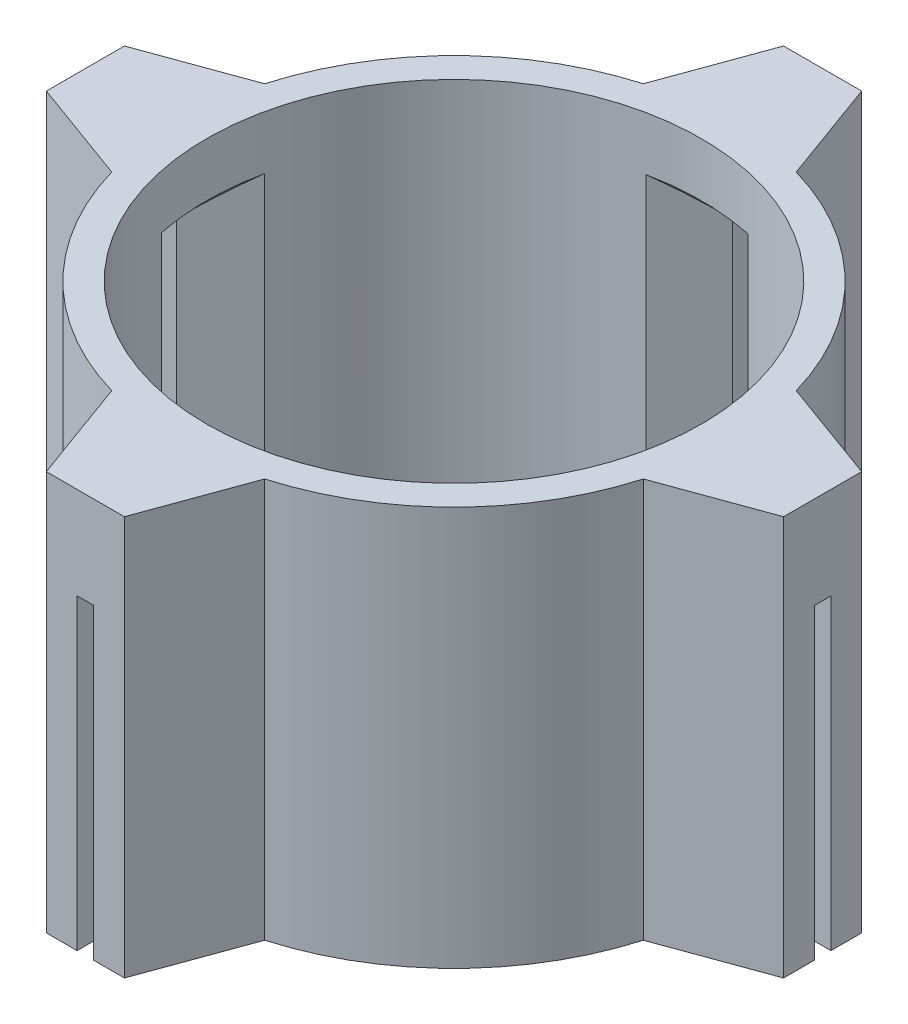
SolidWorks part; units mm, degrees
ref_plane "Front Plane" through (0, 0, 0) normal (0, 0, 1) x (1, 0, 0)
ref_plane "Top Plane" through (0, 0, 0) normal (0, 1, 0) x (1, 0, 0)
ref_plane "Right Plane" through (0, 0, 0) normal (1, 0, 0) x (0, 0, -1)
sketch "Sketch1" plane through (0, 0, 0) normal (0, 1, 0) x (1, 0, 0)
  line L0 (-60.2909, 0) -> (0, 0) construction
  line L1 (0, 49.1127) -> (0, -58.1826) construction
  line L2 (-57.1243, 1.7145) -> (-51.0887, 1.7145)
  line L3 (-57.1243, -1.7145) -> (-51.0887, -1.7145)
  line L4 (51.0887, 1.7145) -> (57.1243, 1.7145)
  line L5 (51.0887, -1.7145) -> (57.1243, -1.7145)
  line L6 (-1.7145, -51.0887) -> (-1.7145, -57.1243)
  line L7 (1.7145, -51.0887) -> (1.7145, -57.1243)
  line L8 (-1.7145, 57.1243) -> (-1.7145, 51.0887)
  line L9 (1.7145, 57.1243) -> (1.7145, 51.0887)
  line L10 (-51.0887, 1.7145) -> (-57.1243, 1.7145)
  line L11 (-51.0887, -1.7145) -> (-57.1243, -1.7145)
  line L12 (57.1243, 1.7145) -> (51.0887, 1.7145)
  line L13 (57.1243, -1.7145) -> (51.0887, -1.7145)
  line L14 (1.7145, 51.0887) -> (1.7145, 57.1243)
  line L15 (-1.7145, 51.0887) -> (-1.7145, 57.1243)
  line L16 (1.7145, -57.1243) -> (1.7145, -51.0887)
  line L17 (-1.7145, -57.1243) -> (-1.7145, -51.0887)
  line L18 (-57.1243, 1.7145) -> (-76.1743, 1.7145)
  line L19 (-76.1743, 1.7145) -> (-76.1743, 8.0645)
  line L20 (-76.1743, 8.0645) -> (-54.9227, 15.7995)
  line L21 (-57.1243, -1.7145) -> (-76.1743, -1.7145)
  line L22 (-76.1743, -1.7145) -> (-76.1743, -8.0645)
  line L23 (-76.1743, -8.0645) -> (-54.9227, -15.7995)
  line L24 (8.0645, 76.1743) -> (15.7995, 54.9227)
  line L25 (1.7145, 76.1743) -> (8.0645, 76.1743)
  line L26 (1.7145, 57.1243) -> (1.7145, 76.1743)
  line L27 (-1.7145, 76.1743) -> (-8.0645, 76.1743)
  line L28 (-1.7145, 57.1243) -> (-1.7145, 76.1743)
  line L29 (-8.0645, 76.1743) -> (-15.7995, 54.9227)
  line L30 (76.1743, -8.0645) -> (54.9227, -15.7995)
  line L31 (76.1743, -1.7145) -> (76.1743, -8.0645)
  line L32 (57.1243, -1.7145) -> (76.1743, -1.7145)
  line L33 (76.1743, 1.7145) -> (76.1743, 8.0645)
  line L34 (57.1243, 1.7145) -> (76.1743, 1.7145)
  line L35 (76.1743, 8.0645) -> (54.9227, 15.7995)
  line L36 (-8.0645, -76.1743) -> (-15.7995, -54.9227)
  line L37 (-1.7145, -76.1743) -> (-8.0645, -76.1743)
  line L38 (-1.7145, -57.1243) -> (-1.7145, -76.1743)
  line L39 (1.7145, -76.1743) -> (8.0645, -76.1743)
  line L40 (1.7145, -57.1243) -> (1.7145, -76.1743)
  line L41 (8.0645, -76.1743) -> (15.7995, -54.9227)
  arc A0 (-51.0887, -1.7145) -> (-1.7145, -51.0887) centre (0, 0) ccw
  arc A1 (-54.9227, -15.7995) -> (-15.7995, -54.9227) centre (0, 0) ccw
  arc A2 (-51.0887, -1.7145) -> (-1.7145, -51.0887) centre (0, 0) ccw
  arc A3 (-51.0887, -1.7145) -> (-1.7145, -51.0887) centre (0, 0) ccw
  arc A4 (-51.0887, -1.7145) -> (-1.7145, -51.0887) centre (0, 0) ccw
  arc A5 (-15.7995, 54.9227) -> (-54.9227, 15.7995) centre (0, 0) ccw
  arc A6 (-1.7145, 51.0887) -> (-51.0887, 1.7145) centre (0, 0) ccw
  arc A7 (-1.7145, 51.0887) -> (-51.0887, 1.7145) centre (0, 0) ccw
  arc A8 (-1.7145, 51.0887) -> (-51.0887, 1.7145) centre (0, 0) ccw
  arc A9 (-1.7145, 51.0887) -> (-51.0887, 1.7145) centre (0, 0) ccw
  arc A10 (51.0887, 1.7145) -> (1.7145, 51.0887) centre (0, 0) ccw
  arc A11 (51.0887, 1.7145) -> (1.7145, 51.0887) centre (0, 0) ccw
  arc A12 (51.0887, 1.7145) -> (1.7145, 51.0887) centre (0, 0) ccw
  arc A13 (51.0887, 1.7145) -> (1.7145, 51.0887) centre (0, 0) ccw
  arc A14 (54.9227, 15.7995) -> (15.7995, 54.9227) centre (0, 0) ccw
  arc A15 (1.7145, -51.0887) -> (51.0887, -1.7145) centre (0, 0) ccw
  arc A16 (1.7145, -51.0887) -> (51.0887, -1.7145) centre (0, 0) ccw
  arc A17 (1.7145, -51.0887) -> (51.0887, -1.7145) centre (0, 0) ccw
  arc A18 (1.7145, -51.0887) -> (51.0887, -1.7145) centre (0, 0) ccw
  arc A19 (15.7995, -54.9227) -> (54.9227, -15.7995) centre (0, 0) ccw
  point P45 (0, 0)
  point P55 (0, 0)
  dimension "D1" = 102.235
  dimension "D2" = 114.3
  dimension "D3" = 3.429
  dimension "D4" = 4
  dimension "D5" = 19.05
  dimension "D6" = 6.35
  dimension "D7" = 70
  dimension "D8" = 4
extrude "Boss-Extrude1" add sketch "Sketch1" along normal blind 63.5 contours A6 L8 A5 L2 | L3 A1 L6 A0 | L7 A19 L5 A15 | L4 A14 L9 A10
sketch "Sketch2" plane through (0, 63.5, 0) normal (0, 1, 0) x (1, 0, 0)
  line L0 (-15.7995, 54.9227) -> (-8.0645, 76.1743)
  line L1 (-8.0645, 76.1743) -> (-1.7145, 76.1743)
  line L2 (-1.7145, 76.1743) -> (8.0645, 76.1743)
  line L3 (8.0645, 76.1743) -> (15.7995, 54.9227)
  line L4 (54.9227, 15.7995) -> (76.1743, 8.0645)
  line L5 (76.1743, 8.0645) -> (76.1743, -8.0645)
  line L6 (76.1743, -8.0645) -> (54.9227, -15.7995)
  line L7 (15.7995, -54.9227) -> (8.0645, -76.1743)
  line L8 (8.0645, -76.1743) -> (-8.0645, -76.1743)
  line L9 (-8.0645, -76.1743) -> (-15.7995, -54.9227)
  line L10 (-54.9227, -15.7995) -> (-76.1743, -8.0645)
  line L11 (-76.1743, -8.0645) -> (-76.1743, 8.0645)
  line L12 (-76.1743, 8.0645) -> (-54.9227, 15.7995)
  circle A0 centre (0, 0) radius 51.1175
  arc A1 (-54.9227, -15.7995) -> (-15.7995, -54.9227) centre (0, 0) ccw
  arc A2 (-1.7145, 51.0887) -> (-51.0887, 1.7145) centre (0, 0) ccw construction
  arc A3 (-15.7995, 54.9227) -> (-54.9227, 15.7995) centre (0, 0) ccw construction
  arc A4 (15.7995, -54.9227) -> (54.9227, -15.7995) centre (0, 0) ccw
  arc A5 (54.9227, 15.7995) -> (15.7995, 54.9227) centre (0, 0) ccw
  arc A6 (-15.7995, 54.9227) -> (-54.9227, 15.7995) centre (0, 0) ccw
extrude "Boss-Extrude2" add sketch "Sketch2" along normal blind 19.05
chamfer "Chamfer4" distance 7.9375 angle 45 12 edges at (51.0887, 31.75, 1.7145) (51.0887, 31.75, -1.7145) (51.1175, 63.5, 0) (-1.7145, 31.75, -51.0887) (1.7145, 31.75, -51.0887) (0, 63.5, -51.1175) (-51.0887, 31.75, 1.7145) (-51.0887, 31.75, -1.7145) (-51.1175, 63.5, 0) (0, 63.5, 51.1175) (-1.7145, 31.75, 51.0887) (1.7145, 31.75, 51.0887)
